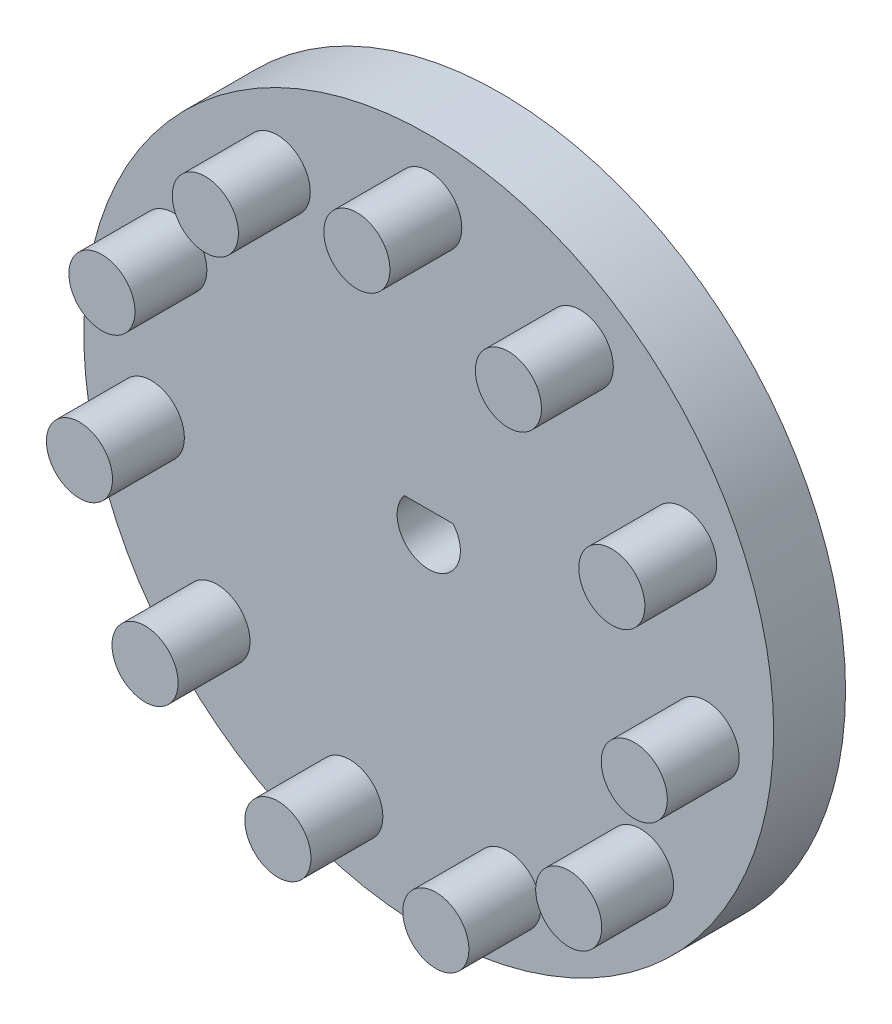
SolidWorks part; units mm, degrees
ref_plane "Front Plane" through (0, 0, 0) normal (0, 0, 1) x (1, 0, 0)
ref_plane "Top Plane" through (0, 0, 0) normal (0, 1, 0) x (1, 0, 0)
ref_plane "Right Plane" through (0, 0, 0) normal (1, 0, 0) x (0, 0, -1)
sketch "Sketch1" plane through (0, 0, 0) normal (0, 0, 1) x (1, 0, 0)
  line L0 (0, 0) -> (0, 24.2305) construction
  line L3 (-1.0795, 0.8867) -> (1.0795, 0.8867)
  circle A0 centre (0, 0) radius 15.24
  circle A1 centre (0, 12.3825) radius 1.5875 construction
  circle A2 centre (0, 12.3825) radius 1.4605
  arc A4 (-1.0795, 0.8867) -> (1.0795, 0.8867) centre (0, 0) ccw
  dimension "D1" = 30.48
  dimension "D3" = 1.27
  dimension "D4" = 2.921
  dimension "D6" = 2.794
  dimension "D2" = 3.175
  dimension "D7" = 2.159
extrude "Boss-Extrude1" add sketch "Sketch1" along normal blind 3.175
extrude "Boss-Extrude4" add sketch "Sketch1<7>" along normal blind 6.35 contours A2 region at (0, 12.3825, 0)
sketch "Sketch1<7>" plane through (0, 0, 0) normal (0, 0, 1) x (1, 0, 0) same geometry as "Sketch1"
pattern_circular "CirPattern4" count 11 over 360 about axis through (0, 0, 3.175) along (0, 0, -1) of "Boss-Extrude4"
